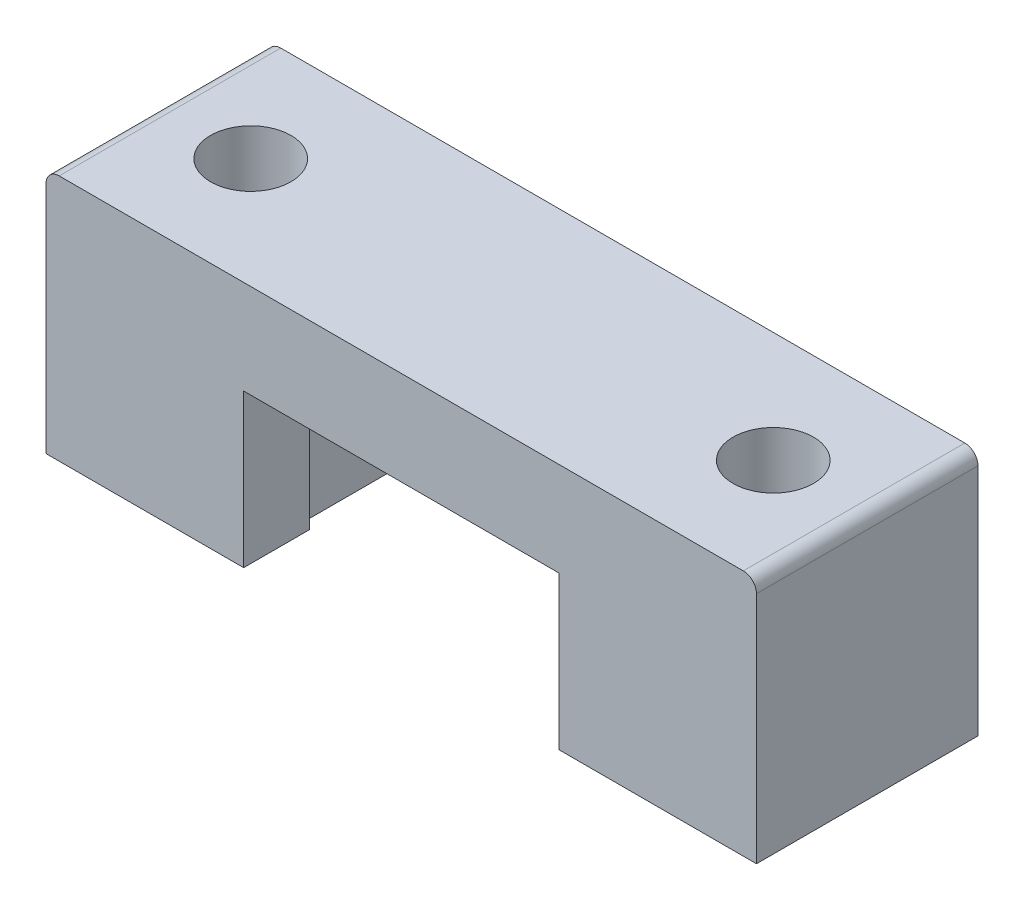
SolidWorks part; units mm, degrees
ref_plane "Front Plane" through (0, 0, 0) normal (0, 0, 1) x (1, 0, 0)
ref_plane "Top Plane" through (0, 0, 0) normal (0, 1, 0) x (1, 0, 0)
ref_plane "Right Plane" through (0, 0, 0) normal (1, 0, 0) x (0, 0, -1)
sketch "Sketch1" plane through (0, 0, 0) normal (0, 1, 0) x (1, 0, 0)
  line L0 (0, 0) -> (0, -6)
  line L1 (0, -6) -> (0.375, -6)
  line L2 (0.375, -6) -> (0.375, -8.54)
  line L3 (0.375, -8.54) -> (12.525, -8.54)
  line L4 (12.525, -8.54) -> (12.525, -6)
  line L5 (12.525, -6) -> (12.9, -6)
  line L6 (12.9, -6) -> (12.9, 0)
  line L7 (12.9, 0) -> (0, 0)
  line L8 (0, 0) -> (-7.245, 0)
  line L9 (-7.245, 0) -> (-7.245, -8.54)
  line L10 (-7.245, -8.54) -> (0.375, -8.54)
  line L11 (12.9, 0) -> (20.145, 0)
  line L12 (20.145, 0) -> (20.145, -8.54)
  line L13 (20.145, -8.54) -> (12.525, -8.54)
  circle A0 centre (-3.6225, -4.27) radius 1.55
  circle A1 centre (16.5225, -4.27) radius 1.55
  point P17 (-3.4674, -3.4288)
  point P18 (0, 0)
  point P19 (20.145, -4.27)
  point P20 (-3.1427, -4.27)
  point P21 (-3.6225, 0)
  point P22 (0, 0)
  point P23 (16.5225, 0)
  dimension "D7" = 3.1
  dimension "D1" = 2.54
  dimension "D2" = 6
  dimension "D3" = 12.9
  dimension "D4" = 0.375
  dimension "D5" = 0.375
  dimension "D6" = 7.62
extrude "Boss-Extrude1" add sketch "Sketch1" along normal blind 9.525 contours L8 L10 L2 L1 L0 | L6 L7 L0 L1 L2 L3 L4 L5 | L11 L6 L5 L4 L13 | L8 L9 L10 | L11 L13 L12 region at (6.45, 0, 4.2172) region at (-0.1145, 0, 3) region at (16.5225, 0, 0.1145)
extrude "Cut-Extrude1" cut sketch "Sketch1<4>" along normal blind 5.9 contours L6 L7 L0 L1 L2 L3 L4 L5 region at (6.45, 0, 4.2172)
sketch "Sketch1<4>" plane through (0, 0, 0) normal (0, 1, 0) x (1, 0, 0) same geometry as "Sketch1"
fillet "Fillet1" radius 0.508 2 edges at (-7.245, 9.525, 4.27) (20.145, 9.525, 4.27)
